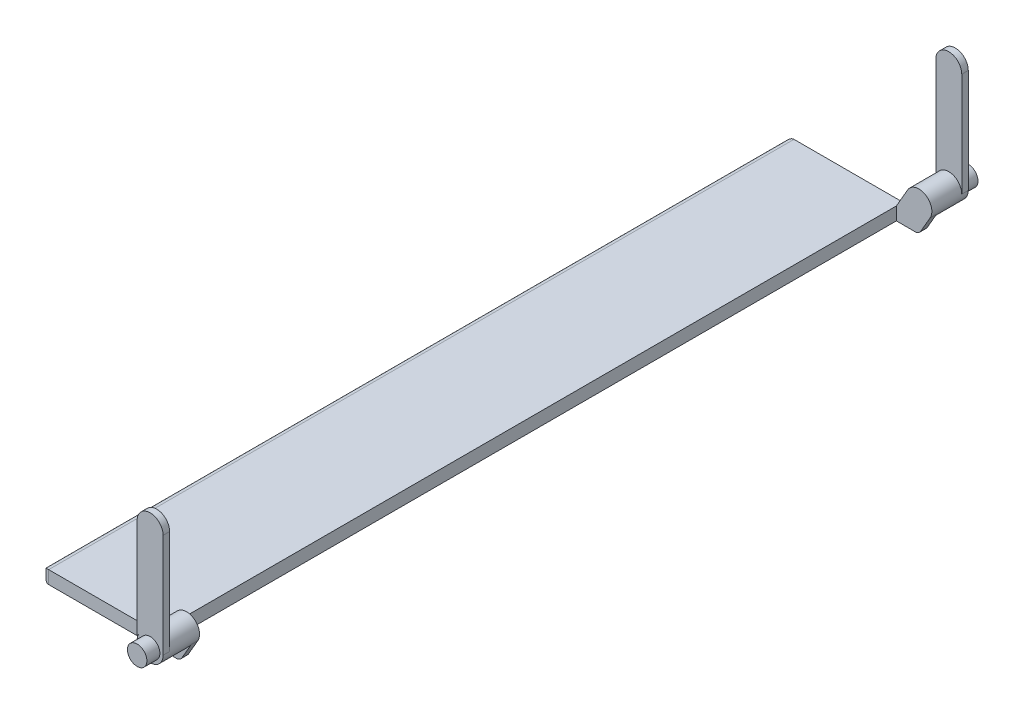
SolidWorks part; units mm, degrees
material "ABS"
ref_plane "Front Plane" through (0, 0, 0) normal (0, 0, 1) x (1, 0, 0)
ref_plane "Top Plane" through (0, 0, 0) normal (0, 1, 0) x (1, 0, 0)
ref_plane "Right Plane" through (0, 0, 0) normal (1, 0, 0) x (0, 0, -1)
sketch "Sketch1" plane through (0, 0, 0) normal (0, 0, 1) x (1, 0, 0)
  point P0 (0, 0)
  line B0 (-33.7058, -6.35) -> (-33.7058, -3.175)
  line B1 (-33.7058, -6.35) -> (0, -6.35)
  line B2 (0, -6.35) -> (2.7496, -1.5875)
  line B3 (-33.7058, -3.175) -> (-5.4993, -3.175)
  line B4 (-2.7496, 1.5875) -> (-5.4993, -3.175)
  circle B5 centre (0, 0) radius 2.3812
  circle B6 centre (0, 0) radius 3.175
sketch_block_instance "trap_door_geometry-1"
sketch_block "trap_door_geometry" parameters "D1"=4.7625, "D2"=6.35
extrude "Boss-Extrude1" add sketch "Sketch1" along normal mid plane 182.2196 contours B6 B4 B3 B0 B1 B2 | B6 B5 | B5 region at (-15.5478, -4.5785, 0) region at (-1.5426, -2.6719, 0) region at (0, 0, 0)
sketch "Sketch2" plane through (0, 0, 0) normal (0, 1, 0) x (1, 0, 0)
  line L0 (-5.4993, -91.1098) -> (-5.4993, 91.1098) construction
  line L1 (3.175, -91.1098) -> (3.175, 91.1098) construction
  line L2 (-5.4993, -91.1098) -> (-5.4993, 91.1098)
  line L3 (3.175, -91.1098) -> (3.175, 91.1098)
  line L4 (3.175, -89.5223) -> (-5.4993, -89.5223)
  line L5 (-2.7496, -91.1098) -> (3.175, -91.1098) construction
  line L6 (0, 0) -> (50000, 0) construction
  line L7 (3.175, 89.5223) -> (-5.4993, 89.5223)
  dimension "D1" = 1.5875
extrude "Cut-Extrude1" cut sketch "Sketch2" against normal through all both and the other way through all contours L2 L6 L3 L7 | L6 L2 L4 L3 region at (-1.1621, 0, 0)
fillet "Fillet1" radius 1.5875 6 edges at (0, -6.35, -90.3161) (0, -6.35, 90.3161) (-33.7058, -4.7625, 91.1098) (-33.7058, -6.35, 0) (-33.7058, -3.175, 0) (-33.7058, -4.7625, -91.1098)
sketch "Sketch3" plane through (0, 0, 91.1098) normal (0, 0, 1) x (1, 0, 0)
  circle A0 centre (0, 0) radius 3.175
  dimension "D1" = 6.35
extrude "Boss-Extrude2" add sketch "Sketch3" along normal blind 7.3152
sketch "Sketch4" plane through (0, 0, 98.425) normal (0, 0, 1) x (1, 0, 0)
  circle A0 centre (0, 0) radius 2.3813
  dimension "D1" = 4.7625
extrude "Boss-Extrude3" add sketch "Sketch4" along normal blind 3.175
mirror "Mirror1" about plane through (0, 0, 0) normal (0, 0, 1) of "Boss-Extrude2", "Boss-Extrude3"
sketch "Sketch6" plane through (0, 0, -98.425) normal (0, 0, -1) x (-1, 0, 0)
  line L0 (0, 0) -> (0, 50000) construction
  line L1 (2.7496, 1.5875) -> (5.4993, -3.175) construction
  line L2 (2.7496, 1.5875) -> (3.175, 0.8507)
  line L3 (-3.175, 25.4) -> (-3.175, 0)
  line L4 (3.175, 25.4) -> (3.175, 0.8507)
  circle A0 centre (0, 0) radius 3.175 construction
  arc A1 (2.7496, 1.5875) -> (-3.175, 0) centre (0, 0) ccw
  arc A2 (3.175, 25.4) -> (-3.175, 25.4) centre (0, 25.4) ccw
  dimension "D1" = 6.35
  dimension "D2" = 25.4
extrude "Boss-Extrude4" add sketch "Sketch6" against normal blind 1.5875
mirror "Mirror2" about plane through (0, 0, 0) normal (0, 0, 1) of "Boss-Extrude4"
